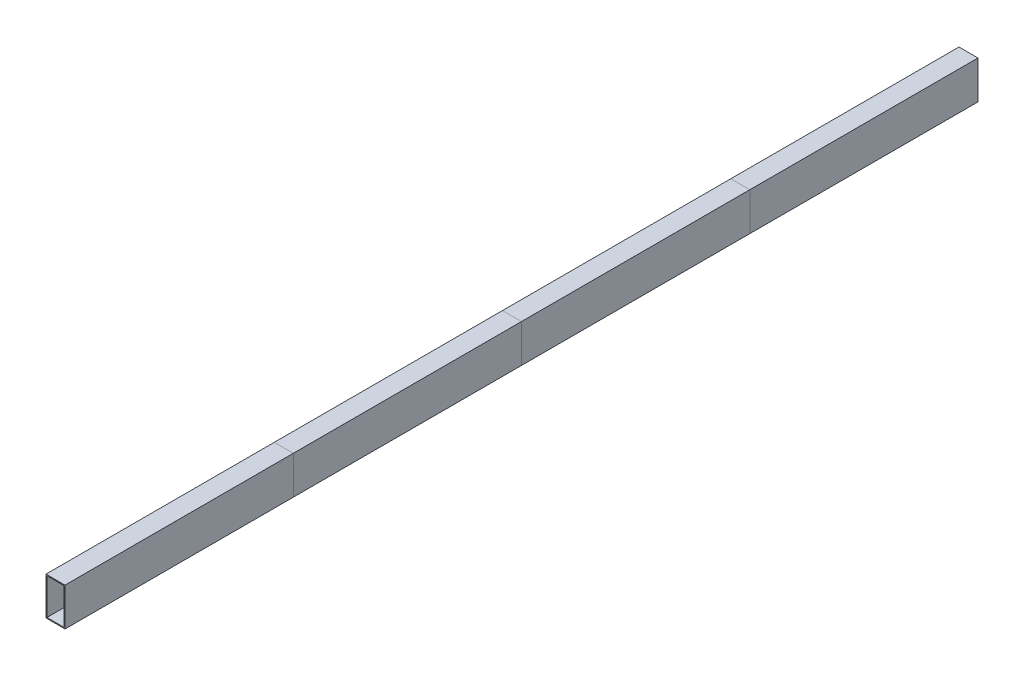
SolidWorks part; units mm, degrees
ref_plane "Спереди" through (0, 0, 0) normal (0, 0, 1) x (1, 0, 0)
ref_plane "Сверху" through (0, 0, 0) normal (0, 1, 0) x (1, 0, 0)
ref_plane "Справа" through (0, 0, 0) normal (1, 0, 0) x (0, 0, -1)
sketch "Эскиз1" plane through (0, 0, 0) normal (0, 0, 1) x (1, 0, 0)
  line L1 (-50, -100) -> (50, -100)
  line L2 (-50, -100) -> (-50, 100)
  line L3 (-50, 100) -> (50, 100)
  line L4 (50, -100) -> (50, 100)
  line L5 (-50, -100) -> (50, 100) construction
  line L6 (-50, 100) -> (50, -100) construction
  line L7 (-45, -95) -> (45, -95)
  line L8 (-45, -95) -> (-45, 95)
  line L9 (-45, 95) -> (45, 95)
  line L10 (45, -95) -> (45, 95)
  line L11 (-45, -95) -> (45, 95) construction
  line L12 (-45, 95) -> (45, -95) construction
  point P0 (0, 0)
  point P6 (0, 0)
  point P11 (0, 100)
  point P12 (0, -100)
  dimension "D1" = 100
  dimension "D2" = 200
  dimension "D3" = 90
  dimension "D4" = 190
extrude "Бобышка-Вытянуть1" add sketch "Эскиз1" along normal blind 1200
extrude "Бобышка-Вытянуть2" add sketch "Эскиз1<2>" along normal blind 1200 from surface separate body starting at face at (0, 0, 1200)
sketch "Эскиз1<2>" plane through (0, 0, 0) normal (0, 0, 1) x (1, 0, 0) same geometry as "Эскиз1"
extrude "Бобышка-Вытянуть3" add sketch "Эскиз1<3>" along normal blind 1200 from surface separate body starting at face at (0, 0, 2400)
sketch "Эскиз1<3>" plane through (0, 0, 0) normal (0, 0, 1) x (1, 0, 0) same geometry as "Эскиз1"
extrude "Бобышка-Вытянуть4" add sketch "Эскиз1<4>" along normal blind 1200 from surface separate body starting at face at (0, 0, 3600)
sketch "Эскиз1<4>" plane through (0, 0, 0) normal (0, 0, 1) x (1, 0, 0) same geometry as "Эскиз1"
ref_point "Точка1" parameters "D1"=50
ref_point "Точка2"
